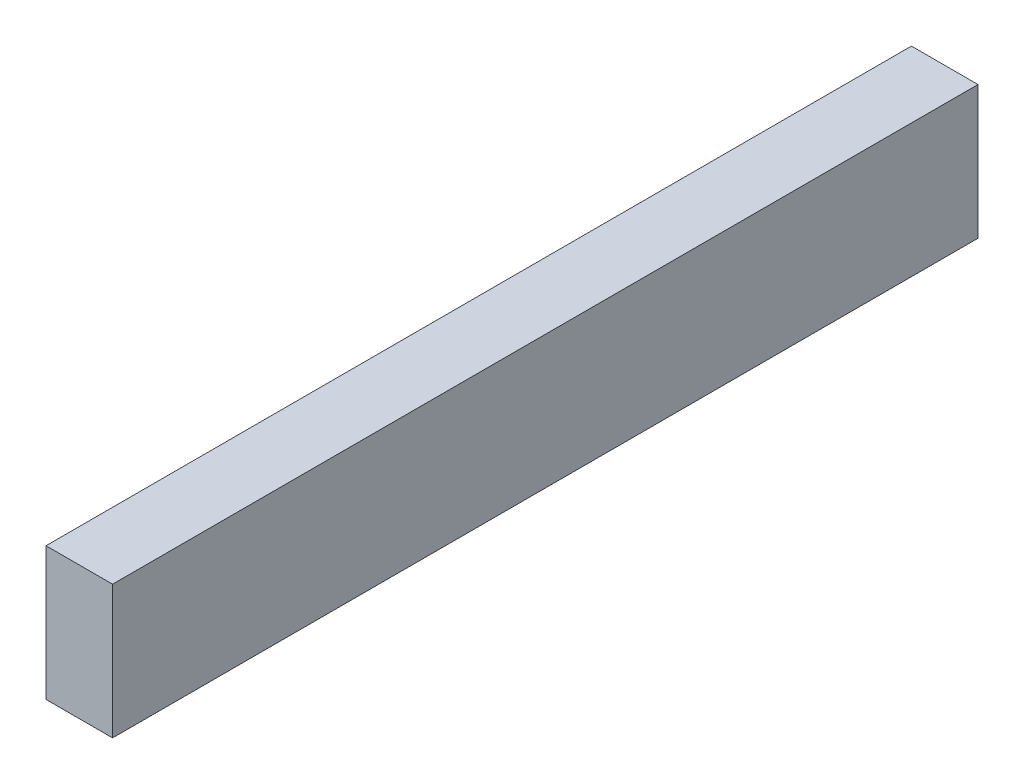
SolidWorks part; units mm, degrees
material "Pine"
ref_plane "Front Plane" through (0, 0, 0) normal (0, 0, 1) x (1, 0, 0)
ref_plane "Top Plane" through (0, 0, 0) normal (0, 1, 0) x (1, 0, 0)
ref_plane "Right Plane" through (0, 0, 0) normal (1, 0, 0) x (0, 0, -1)
sketch "Sketch1" plane through (0, 0, 0) normal (0, 0, 1) x (1, 0, 0)
  line L1 (0, 0) -> (40, 0)
  line L2 (0, 0) -> (0, -80)
  line L3 (0, -80) -> (40, -80)
  line L4 (40, 0) -> (40, -80)
  dimension "D1" = 40
  dimension "D2" = 80
extrude "Boss-Extrude1" add sketch "Sketch1" along normal blind 520
